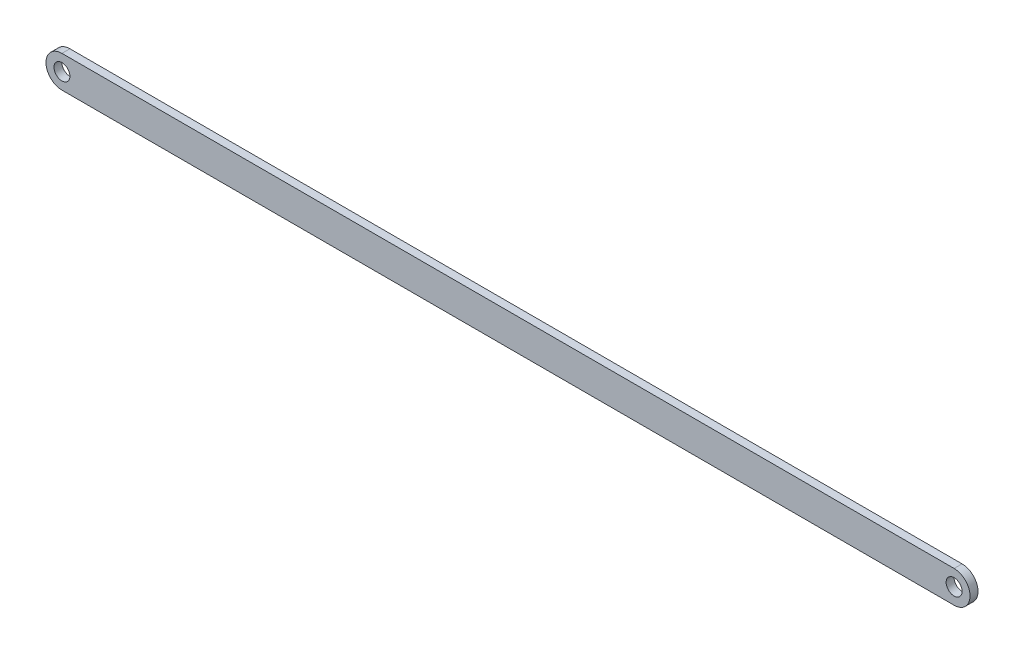
SolidWorks part; units mm, degrees
ref_plane "Front" through (0, 0, 0) normal (0, 0, 1) x (1, 0, 0)
ref_plane "Top" through (0, 0, 0) normal (0, 1, 0) x (1, 0, 0)
ref_plane "Right" through (0, 0, 0) normal (1, 0, 0) x (0, 0, -1)
sketch "Sketch1" plane through (0, 0, 0) normal (0, 0, 1) x (1, 0, 0)
  line L0 (0, 0) -> (355.6, 0)
  line L2 (355.6, 12.7) -> (0, 12.7)
  arc A0 (0, 12.7) -> (0, 0) centre (0, 6.35) ccw
  arc A1 (355.6, 12.7) -> (355.6, 0) centre (355.6, 6.35) cw
  dimension "D1" = 355.6
  dimension "D2" = 12.7
extrude "Boss-Extrude1" add sketch "Sketch1" along normal blind 3.175
hole_wizard "1/4 (0.25) Diameter Hole2" positions "Sketch5" profile "Sketch6" hole size "1/4" standard "ANSI Inch" end condition through all
sketch "Sketch5" plane through (0, 0, 0) normal (0, 0, -1) x (-1, 0, 0)
  point P0 (0, 6.35)
  point P2 (-355.6, 6.35)
  point P6 (0, 6.35)
sketch "Sketch6" plane through (0, 6.35, 0) normal (1, 0, 0) x (0, 1, 0)
  line L0 (0, 0) -> (0, 3.175)
  line L1 (0, 3.175) -> (3.175, 3.175)
  line L2 (3.175, 3.175) -> (3.175, 0)
  line L5 (3.175, 0) -> (0, 0)
  line L11 (0, -6.35) -> (0, 107.95) construction
  dimension "Thru Hole Dia." = 6.35
  dimension "Thru Hole Depth" = 3.175
